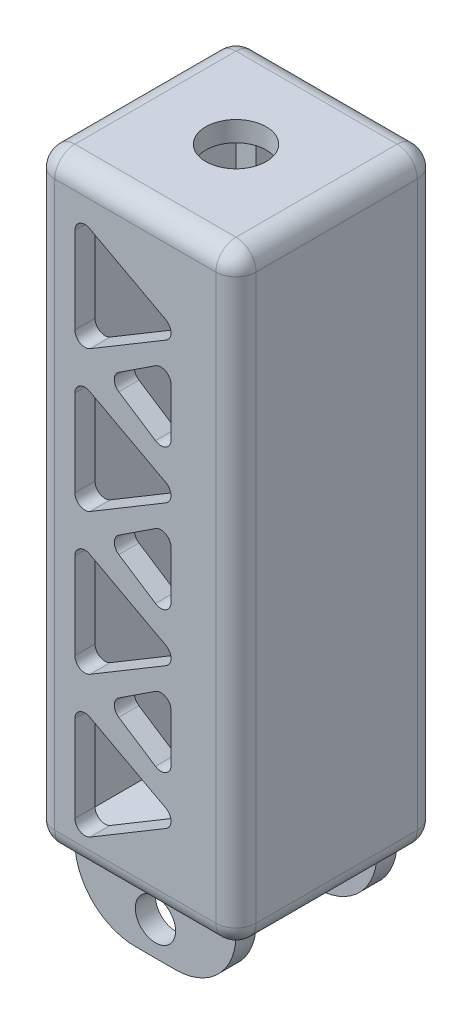
SolidWorks part; units mm, degrees
ref_plane "Front Plane" through (0, 0, 0) normal (0, 0, 1) x (1, 0, 0)
ref_plane "Top Plane" through (0, 0, 0) normal (0, 1, 0) x (1, 0, 0)
ref_plane "Right Plane" through (0, 0, 0) normal (1, 0, 0) x (0, 0, -1)
sketch "Sketch1" plane through (0, 0, 0) normal (0, 0, 1) x (1, 0, 0)
  line L1 (5, 15) -> (-5, 15)
  line L2 (5, 15) -> (5, -15)
  line L3 (5, -15) -> (-5, -15)
  line L4 (-5, 15) -> (-5, -15)
  line L5 (5, 15) -> (-5, -15) construction
  line L6 (5, -15) -> (-5, 15) construction
  point P0 (0, 0)
  dimension "D1" = 30
  dimension "D2" = 10
extrude "Boss-Extrude1" add sketch "Sketch1" along normal blind 10
fillet "Fillet2" radius 1 12 edges at (5, -15, 5) (5, 15, 5) (0, 15, 10) (5, 0, 10) (0, -15, 10) (-5, 15, 5) (-5, 0, 10) (-5, -15, 5) (0, -15, 0) (5, 0, 0) (0, 15, 0) (-5, 0, 0)
ref_plane "Plane1" through (0, 14, 0) normal (0, 1, 0) x (1, 0, 0)
sketch "Sketch2" plane through (0, 14, 0) normal (0, 1, 0) x (1, 0, 0)
  line L1 (-4, -1) -> (4, -1)
  line L2 (-4, -1) -> (-4, -9)
  line L3 (-4, -9) -> (4, -9)
  line L4 (4, -1) -> (4, -9)
extrude "Cut-Extrude1" cut sketch "Sketch2" against normal blind 28
sketch "Sketch4" plane through (0, 15, 0) normal (0, 1, 0) x (1, 0, 0)
  circle A0 centre (0, -5) radius 1.5
  dimension "D1" = 3
extrude "Cut-Extrude2" cut sketch "Sketch4" against normal blind 8
sketch "Sketch5" plane through (0, 0, 10) normal (0, 0, 1) x (1, 0, 0)
  line L0 (-2.2636, 12.7368) -> (1.5101, 10.7122)
  line L1 (-4, 14) -> (-4, -14) construction
  line L2 (-3, 12.2962) -> (-3, 8.0137)
  line L3 (-2.2433, 7.5846) -> (1.5305, 9.8426)
  arc A0 (-2.2433, 7.5846) -> (-3, 8.0137) centre (-2.5, 8.0137) cw
  arc A1 (-2.2636, 12.7368) -> (-3, 12.2962) centre (-2.5, 12.2962) ccw
  arc A2 (1.5101, 10.7122) -> (1.5305, 9.8426) centre (1.2737, 10.2716) cw
  point P7 (-3, 7.1318)
  point P10 (-3, 13.1318)
  point P13 (2.2872, 10.2954)
  dimension "D4" = 0.5
  dimension "D1" = 1
  dimension "D2" = 6
  dimension "D3" = 6
extrude "Cut-Extrude3" cut sketch "Sketch5" against normal through all
pattern_linear "LPattern1" count 4 spacing 7 along (0, -1, 0) of "Cut-Extrude3"
sketch "Sketch6" plane through (0, 0, 0) normal (0, 0, -1) x (-1, 0, 0)
  line L0 (-1.7737, 8.0538) -> (-1.7737, 5.6713)
  line L1 (-0.9997, 5.2531) -> (0.818, 6.4443)
  line L2 (0.818, 7.2807) -> (-0.9997, 8.472)
  arc A0 (-1.7737, 5.6713) -> (-0.9997, 5.2531) centre (-1.2737, 5.6713) ccw
  arc A1 (-0.9997, 8.472) -> (-1.7737, 8.0538) centre (-1.2737, 8.0538) ccw
  arc A2 (0.818, 6.4443) -> (0.818, 7.2807) centre (0.5439, 6.8625) ccw
  dimension "D1" = 0.5
extrude "Cut-Extrude4" cut sketch "Sketch6" against normal through all
pattern_linear "LPattern2" count 3 spacing 7 along (0, -1, 0) of "Cut-Extrude4"
sketch "Sketch7" plane through (0, -15, 0) normal (0, -1, 0) x (1, 0, 0)
  line L0 (4, 1) -> (4, 9) construction
  line L1 (-4, 9) -> (4, 9)
  line L2 (-4, 9) -> (-4, 8)
  line L3 (-4, 8) -> (4, 8)
  line L4 (4, 9) -> (4, 8)
  dimension "D1" = 1
extrude "Boss-Extrude2" add sketch "Sketch7" along normal blind 3
fillet "Fillet4" radius 3 2 edges at (4, -18, 8.5) (-4, -18, 8.5)
pattern_linear "LPattern3" count 2 spacing 7 along (0, 0, -1) of "Boss-Extrude2"
fillet "Fillet5" radius 3 2 edges at (4, -18, 1.5) (-4, -18, 1.5)
sketch "Sketch8" plane through (0, 0, 9) normal (0, 0, 1) x (1, 0, 0)
  circle A0 centre (0, -16.3383) radius 1
  dimension "D1" = 2
extrude "Cut-Extrude5" cut sketch "Sketch8" against normal through all
